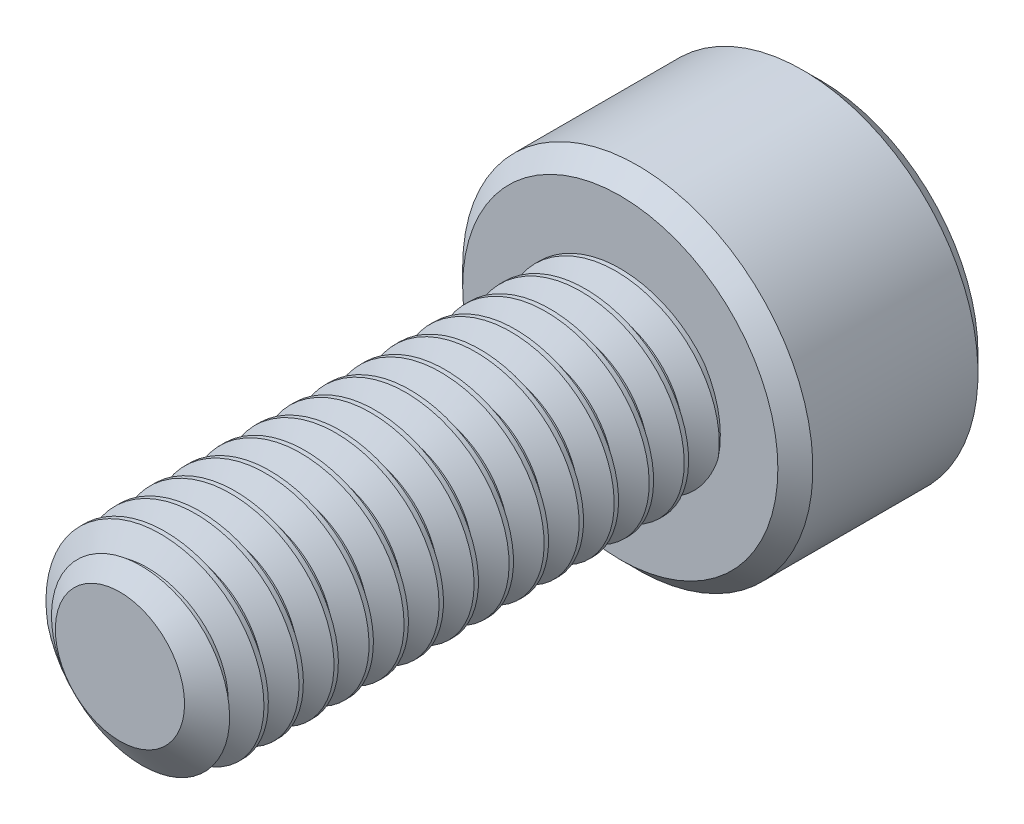
SolidWorks part; units mm, degrees
other "DetailItem1"
ref_plane "Front Plane" through (0, 0, 0) normal (0, 0, 1) x (1, 0, 0)
ref_plane "Top Plane" through (0, 0, 0) normal (0, 1, 0) x (1, 0, 0)
ref_plane "Right Plane" through (0, 0, 0) normal (1, 0, 0) x (0, 0, -1)
sketch "Sketch1" plane through (0, 0, 0) normal (0, 0, 1) x (1, 0, 0)
  circle A0 centre (0, 0) radius 2
  dimension "OD" = 4
extrude "Extrude1" add sketch "Sketch1" against normal blind 10
sketch "Sketch2" plane through (0, 0, 0) normal (0, 0, 1) x (1, 0, 0)
  circle A0 centre (0, 0) radius 2 construction
  circle A1 centre (0, 0) radius 2
curve "Helix/Spiral1" pitch 0.7 height 10.7 radius 2 centre (0, 0, 0) axis (0, 0, -1) start towards (0, 1, 0) parameters "pitch"=0.7
sketch "Sketch3" plane through (0, 0, 0) normal (1, 0, 0) x (0, 0, -1)
  line L0 (-0.6125, 2) -> (-0.35, 1.5453)
  line L1 (-0.35, 1.5453) -> (-0.2625, 1.5453)
  line L2 (-0.2625, 1.5453) -> (0, 2)
  line L3 (-0.6125, 2) -> (0, 2)
  line L4 (-0.3062, 2) -> (-0.3062, 1.5453) construction
  line L5 (-0.4812, 1.7727) -> (-0.1312, 1.7727) construction
  line L6 (0, 2) -> (0, -2) construction
  dimension "D1" = 0.0875
  dimension "D2" = 0.35
  dimension "D3" = 60
sweep "Cut-Sweep1" cut profiles "Sketch3" path "Helix/Spiral1"
sketch "Sketch4" plane through (0, 0, 0) normal (1, 0, 0) x (0, 0, -1)
  line L0 (0.4962, 2) -> (0, 1.2913)
  line L1 (0, 1.2913) -> (0, 2)
  line L2 (0.4962, 2) -> (0, 2)
  line L3 (-0.6125, 2) -> (0, 2) construction
  line L4 (0, 0) -> (7.0209, 0) construction
  dimension "D1" = 55
  dimension "D2" = 0.254
revolve "Cut-Revolve1" cut sketch "Sketch4" angle 360 about L4
sketch "Sketch6" plane through (0, 0, -10) normal (0, 0, -1) x (-1, 0, 0)
  circle A0 centre (0, 0) radius 3.5
  dimension "head dia" = 7
extrude "Extrude2" add sketch "Sketch6" along normal blind 4
sketch "Sketch7" plane through (0, 0, -14) normal (0, 0, -1) x (-1, 0, 0)
  line L1 (0, 1.7321) -> (-1.5, 0.866)
  line L2 (-1.5, 0.866) -> (-1.5, -0.866)
  line L3 (-1.5, -0.866) -> (0, -1.7321)
  line L4 (0, -1.7321) -> (1.5, -0.866)
  line L5 (1.5, -0.866) -> (1.5, 0.866)
  line L6 (1.5, 0.866) -> (0, 1.7321)
  circle A0 centre (0, 0) radius 1.5 construction
  dimension "hex dia" = 3
extrude "Cut-Extrude1" cut sketch "Sketch7" against normal blind 2.25
sketch "Sketch8" plane through (0, 0, -14) normal (0, 0, -1) x (-1, 0, 0)
  circle A0 centre (0, 0) radius 1.7321
extrude "Cut-Extrude2" cut sketch "Sketch8" against normal through all draft 45
chamfer "Chamfer1" distance 0.35 angle 45 2 edges at (-3.5, 0, -14) (-3.5, 0, -10)
sketch "Sketch10" plane through (0, 0, -10) normal (0, 0, 1) x (1, 0, 0)
  circle A1 centre (0, 0) radius 2
  circle A2 centre (0, 0) radius 2
  dimension "D1" = 0
ref_plane "Plane1" through (0, 0, 0) normal (0, 0, 1) x (1, 0, 0)
extrude "partial thread" [suppressed] add sketch "Sketch10" along normal up to surface (10 mm away) separate body up to plane "Plane1"
chamfer "Chamfer2" [suppressed] distance 0.08 angle 45
combine bodies "Combine1" [suppressed] operation type add bodies to combine 107 108
sketch "Sketch9" plane through (0, 0, 0) normal (1, 0, 0) x (0, 0, -1)
  line L0 (0, 2) -> (0, -2) construction
  line L1 (1.75, 2) -> (1.75, -2) construction
  dimension "D1" = 1.75
equation "\"D3@Helix/Spiral1\" = \"screw length@Extrude1\"+\"pitch@Helix/Spiral1\""
equation "\"D1@Sketch3\" = \"pitch@Helix/Spiral1\"*.125"
equation "\"D2@Sketch3\" = \"pitch@Helix/Spiral1\"*.5"
equation "\"D1@Cut-Extrude1\" = \"hex dia@Sketch7\"*.75"
equation "\"D1@Chamfer1\" = \"head dia@Sketch6\"*.05"
equation "\"D1@Sketch9\" = \"pitch@Helix/Spiral1\"*2.5"
equation "\"D1@Chamfer2\"=\"OD@Sketch1\"*.02"
